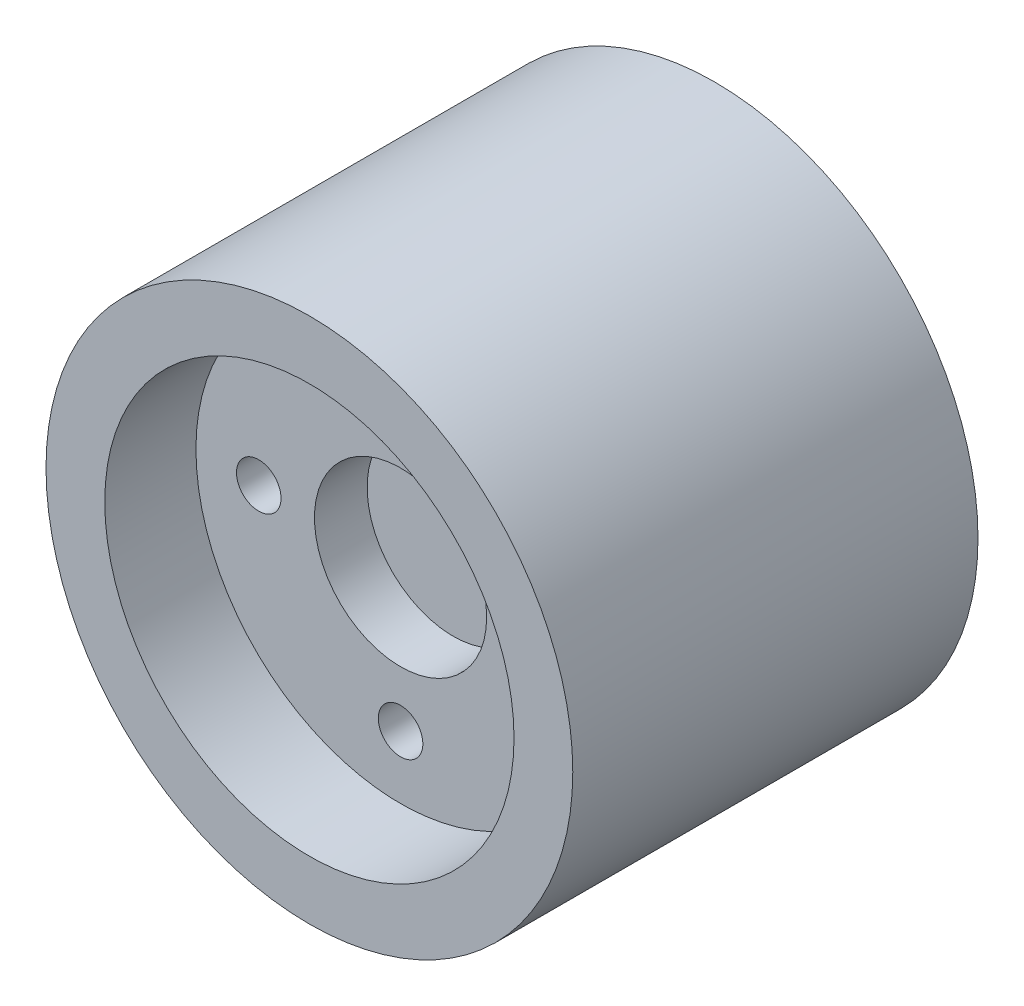
SolidWorks part; units mm, degrees
ref_plane "Front Plane" through (0, 0, 0) normal (0, 0, 1) x (1, 0, 0)
ref_plane "Top Plane" through (0, 0, 0) normal (0, 1, 0) x (1, 0, 0)
ref_plane "Right Plane" through (0, 0, 0) normal (1, 0, 0) x (0, 0, -1)
sketch "Sketch1" plane through (0, 0, 0) normal (0, 0, 1) x (1, 0, 0)
  circle A0 centre (0, 0) radius 13
  dimension "D1" = 26
extrude "Boss-Extrude1" add sketch "Sketch1" along normal blind 20
sketch "Sketch2" plane through (0, 0, 20) normal (0, 0, 1) x (1, 0, 0)
  circle A0 centre (0, 0) radius 10.1
  dimension "D1" = 20.2
extrude "Cut-Extrude1" cut sketch "Sketch2" against normal blind 4.5
sketch "Sketch3" plane through (0, 0, 15.5) normal (0, 0, 1) x (1, 0, 0)
  circle A0 centre (0, 0) radius 4.25
  dimension "D1" = 8.5
extrude "Cut-Extrude2" cut sketch "Sketch3" against normal blind 2.6
sketch "Sketch4" plane through (0, 0, 0) normal (0, 0, -1) x (-1, 0, 0)
  circle A0 centre (0, 0) radius 2.125
  dimension "D1" = 4.25
extrude "Cut-Extrude3" cut sketch "Sketch4" against normal blind 10
sketch "Sketch5" plane through (0, 0, 0) normal (0, 0, -1) x (-1, 0, 0)
  circle A0 centre (0, 7) radius 2
  circle A1 centre (7, 0) radius 2
  circle A2 centre (0, -7) radius 2
  circle A4 centre (-7, 0) radius 2 [skipped]
  circle A5 centre (0, 0) radius 2.125 construction
  point P11 (0, 0)
  dimension "D2" = 4
  dimension "D1" = 7
  dimension "D4" = 7
  dimension "D3" = 4
extrude "Cut-Extrude4" cut sketch "Sketch5" against normal offset from surface (13.5 mm away) 2 up to face at (4.25, 0, 15.5)
sketch "Sketch6" plane through (0, 0, 0) normal (0, 0, -1) x (-1, 0, 0)
  circle A0 centre (0, 7) radius 1.1
  circle A1 centre (7, 0) radius 1.1
  circle A2 centre (0, -7) radius 1.1
  circle A4 centre (-7, 0) radius 1.1 [skipped]
  circle A5 centre (0, 7) radius 2 construction
  point P12 (0, 0)
  dimension "D3" = 4
  dimension "D1" = 2.2
  dimension "D2" = 7
  dimension "D4" = 7
extrude "Cut-Extrude5" cut sketch "Sketch6" against normal through all
sketch "Sketch7" plane through (0, 0, 0) normal (0, 0, -1) x (-1, 0, 0)
  line L0 (0, 0) -> (-20.2439, 0) construction
  circle A0 centre (-6, 5) radius 2
  circle A1 centre (-6, -5) radius 2
  dimension "D3" = 4
  dimension "D1" = 5
  dimension "D2" = 6
extrude "Cut-Extrude6" cut sketch "Sketch7" against normal blind 6
equation "\"L1\"= 120mm'Upper arm"
equation "\"L3\"= 75mm'Wrist→TCP"
equation "\"h0\"= 75mm'Shoulder height"
equation "\"t_link\"= 3mm'Link plate thickness"
equation "\"t_bracket\"= 4mm'Bracket thickness"
equation "\"d_pin\"= 4mm'Pin diameter (M4)"
equation "\"c_fit\"= 0.2mm'Nominal clearance - measured PLA 2026-10-01"
equation "\"L2\"= 120mm'Forearm"
equation "\"c_fit_pivot\"= \"c_fit\" + 0.05mm'Gripper pivot clearance - chosen 0.25 mm 2026-10-01"
equation "\"d_pin_gripper\"= 3mm'Gripper pivot diameter"
equation "\"w_link\"= 20mm'Link plate depth (bending direction)"
equation "\"w_gap\"= 20mm'Twin-plate gap - provisional, set by elbow servo mount"
equation "\"d_boss\"= 13mm'MG996R output boss dia - from downloaded model, verify with calipers"
equation "\"c_boss\"= 1mm'Radial clearance around servo boss"
equation "\"d_servo_hole\"= \"d_boss\" + 2 * \"c_boss\"'Plate clearance hole for servo boss (15 mm)"
equation "\"t_rim\"= 9.5mm'Min material around servo hole (M3 hole + 3 mm webs each side)"
equation "\"w_link_end\"= \"d_servo_hole\" + 2 * \"t_rim\"'Link plate end width at servo end (34 mm)"
equation "\"d_hole_m3\"= \"d_pin_gripper\" + \"c_fit\"'M3 bolt clearance hole (spacer and adapter bolts)"
equation "\"d_hole_pivot\"= \"d_pin\" + \"c_fit_pivot\"'M4 pivot hole where the pin rotates (4.25 mm)"
equation "\"d_horn\"= 20mm'Horn disc diameter (circular horn) - from MG996R model"
equation "\"t_horn\"= 2.3mm'Horn disc thickness"
equation "\"g_horn\"= 2.2mm'Gap from horn disc to plate 2 inner face - from MockShoulder"
equation "\"d_horn_pocket\"= \"d_horn\" + \"c_fit\"'Adapter pocket for horn disc (20.2 mm)"
equation "\"h_horn_pocket\"= \"g_horn\" + \"t_horn\"'Pocket depth from adapter plate-2 face (4.5 mm)"
equation "\"d_horn_screw_cb\"= 8.5mm'Recess for horn centre-screw head (head is 7.5 mm)"
equation "\"h_horn_screw_cb\"= 2.6mm'Recess depth (head is 2.35 mm tall)"
equation "\"d_adapter\"= 26mm'Horn adapter outer diameter"
equation "\"h_adapter\"= \"w_gap\"'Adapter length, fills the plate gap"
equation "\"t_adapter_floor\"= 2mm'Floor under horn disc that the horn screws pass through"
equation "\"d_horn_screw_hole\"= 2.2mm'Clearance for M2 self-tapper through the floor"
equation "\"r_horn_screw\"= 7mm'Horn screw hole radius (14 mm square pattern)"
equation "\"d_access\"= 4mm'Access bore for the M2 screws from the plate-1 side"
equation "\"d_insert_m3\"= 4mm'Hole for M3 heat-set insert - HZYUEGOU M3 inserts are 4.2 OD, hole 4.0; open to 4.1 if too tight"
equation "\"h_insert_m3\"= 6mm'Insert hole depth"
equation "\"x_adapter_bolt\"= 6mm'Adapter bolt offset from pin, along the arm toward its middle"
equation "\"y_adapter_bolt\"= 5mm'Adapter bolt offset from pin, across the arm (+/-)"
equation "\"d_csk_m3\"= 6.4mm'Countersink diameter in plate 1 for M3 flat head (90 deg)"
equation "\"h_pin_bore\"= 10mm'M4 pin engagement depth in the adapter"
equation "\"D1@Sketch1\"=\"d_adapter\""
equation "\"D1@Boss-Extrude1\"=\"w_gap\""
equation "\"D1@Sketch2\"=\"d_horn_pocket\""
equation "\"D1@Sketch3\"=\"d_horn_screw_cb\""
equation "\"D1@Cut-Extrude2\"=\"h_horn_screw_cb\""
equation "\"D1@Sketch4\"=\"d_hole_pivot\""
equation "\"D1@Cut-Extrude3\"=\"h_pin_bore\""
equation "\"D1@Sketch5\"=\"r_horn_screw\""
equation "\"D2@Sketch5\"=\"d_access\""
equation "\"D4@Sketch5\"=\"r_horn_screw\""
equation "\"D1@Cut-Extrude4\"=\"t_adapter_floor\""
equation "\"D1@Sketch6\"=\"d_horn_screw_hole\""
equation "\"D2@Sketch6\"=\"r_horn_screw\""
equation "\"D4@Sketch6\"=\"r_horn_screw\""
equation "\"D1@Sketch7\"=\"y_adapter_bolt\""
equation "\"D2@Sketch7\"=\"x_adapter_bolt\""
equation "\"D3@Sketch7\"=\"d_insert_m3\""
equation "\"D1@Cut-Extrude6\"=\"h_insert_m3\""
equation "\"c_win\"= 0.3mm'Servo window clearance per side in bracket wall A - starting value, tune after a test print"
equation "\"l_servo\"= 40.9mm'MG996R case length without ears - from the model"
equation "\"w_servo\"= 20mm'MG996R case width - from the model"
equation "\"r_servo_short\"= 10mm'Shaft axis to the short end of the case - from the model"
equation "\"r_servo_long\"= \"l_servo\" - \"r_servo_short\"'Shaft axis to the long end of the case (30.9 mm)"
equation "\"l_ear_holes\"= 48.6mm'MG996R ear hole (keyhole slot) spacing along the case - from the model"
equation "\"w_ear_holes\"= 10mm'MG996R ear hole spacing across the case - from the model"
equation "\"a_ear\"= 8.2mm'Servo ear seating face to plate-2 outer face - from MockShoulder (ear face incl. 0.2 edge round)"
equation "\"l_window\"= \"l_servo\" + 2 * \"c_win\"'Wall A window length (41.5 mm)"
equation "\"w_window\"= \"w_servo\" + 2 * \"c_win\"'Wall A window width (20.6 mm)"
equation "\"g_wall_a\"= \"a_ear\" - \"t_bracket\"'Gap behind wall A to plate 2 (4.4 mm) - ear screw heads sit here"
equation "\"g_wall_b\"= 1mm'Plate 1 outer face to wall B - thrust washer"
equation "\"d_axis_turret\"= 34mm'Shoulder axis to turret mounting face - PLACEHOLDER until the turret is designed"
equation "\"t_foot\"= 6mm'Bracket foot thickness"
equation "\"h_wall_top\"= 41.5mm'Wall A top above the shoulder axis (long-end ear holes + 4 mm)"
equation "\"w_wall\"= 30mm'Bracket wall A and B width"
equation "\"w_foot\"= 50mm'Bracket foot width across the walls"
equation "\"t_boss_b\"= 4mm'Extra thickness of the pin boss on the outside of wall B"
equation "\"d_boss_b\"= 12mm'Pin boss diameter on wall B"
equation "\"D1@Cut-Extrude1\"=\"h_horn_pocket\""
